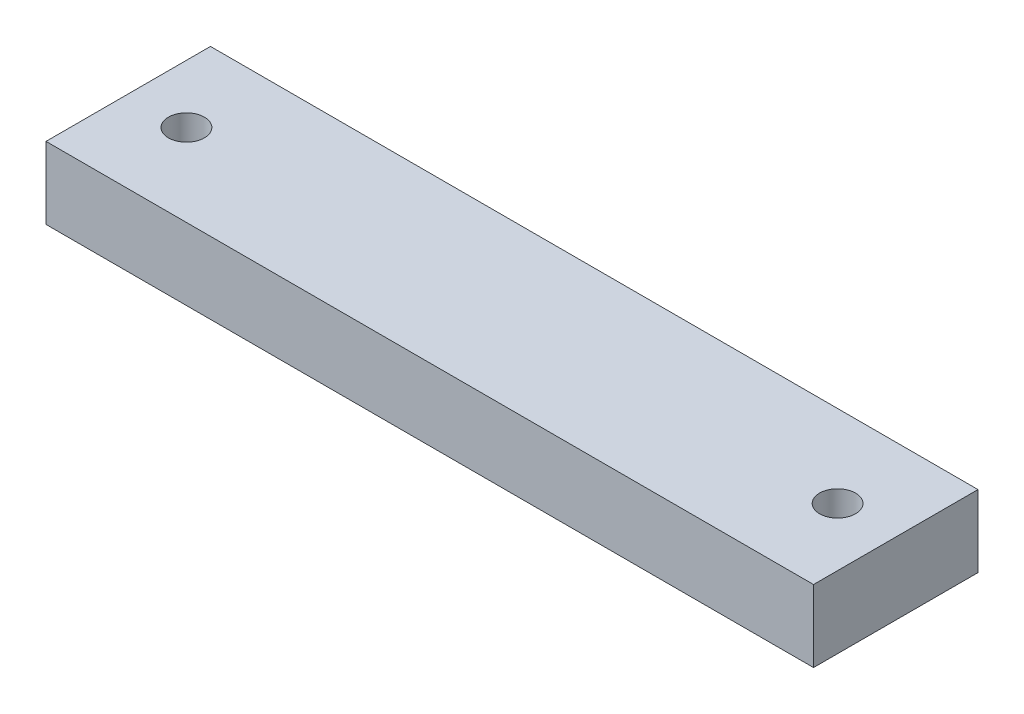
SolidWorks part; units mm, degrees
ref_plane "Front Plane" through (0, 0, 0) normal (0, 0, 1) x (1, 0, 0)
ref_plane "Top Plane" through (0, 0, 0) normal (0, 1, 0) x (1, 0, 0)
ref_plane "Right Plane" through (0, 0, 0) normal (1, 0, 0) x (0, 0, -1)
sketch "Sketch1" plane through (0, 0, 0) normal (0, 1, 0) x (1, 0, 0)
  line L0 (0, 11.43) -> (106.68, 11.43) construction
  line L1 (0, 0) -> (106.68, 0)
  line L2 (0, 0) -> (0, 22.86)
  line L3 (0, 22.86) -> (106.68, 22.86)
  line L4 (106.68, 0) -> (106.68, 22.86)
  line L5 (53.34, 22.86) -> (53.34, 0) construction
  circle A0 centre (8.0899, 11.43) radius 2.5
  circle A1 centre (98.5901, 11.43) radius 2.5
  point P11 (0, 0)
  dimension "D3" = 5
  dimension "D1" = 106.68
  dimension "D2" = 22.86
  dimension "D4" = 45.2501
extrude "Boss-Extrude1" add sketch "Sketch1" along normal blind 10
ref_plane "Plane1" through (53.34, 0, 0) normal (1, 0, 0) x (0, 0, -1)
